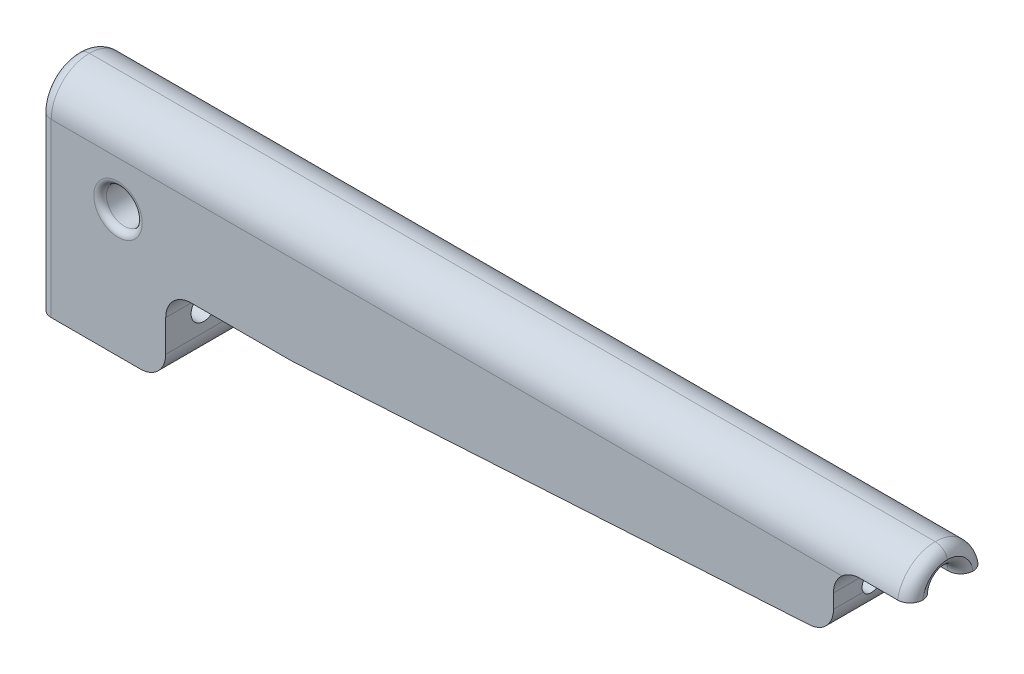
SolidWorks part; units mm, degrees
material "Acetal-Delrin 100 Black"
ref_plane "Front Plane" through (0, 0, 0) normal (0, 0, 1) x (1, 0, 0)
ref_plane "Top Plane" through (0, 0, 0) normal (0, 1, 0) x (1, 0, 0)
ref_plane "Right Plane" through (0, 0, 0) normal (1, 0, 0) x (0, 0, -1)
sketch "Sketch1" plane through (0, 0, 0) normal (0, 0, 1) x (1, 0, 0)
  line L0 (-0.1915, 12.7) -> (-50000.1915, 12.7) construction
  line L1 (25.4, 0) -> (173.99, 0)
  line L2 (0, 0) -> (0, 25.4)
  line L4 (173.99, 0) -> (173.99, 25.4)
  line L5 (173.99, 25.4) -> (0, 25.4)
  line L6 (0, 0) -> (0, -16.51)
  line L7 (0, -16.51) -> (25.4, -16.51)
  line L8 (25.4, -16.51) -> (25.4, 0)
  point P7 (0, 12.7)
  dimension "D1" = 25.4
  dimension "D3" = 16.51
  dimension "D2" = 173.99
  dimension "D4" = 25.4
  dimension "D6" = 25.4
extrude "Boss-Extrude1" add sketch "Sketch1" against normal blind 15.24
fillet "Fillet2" radius 7.62 2 edges at (86.995, 25.4, 0) (86.995, 25.4, -15.24)
sketch "Sketch2" plane through (0, 0, 0) normal (0, 0, 1) x (1, 0, 0)
  line L0 (158.75, 19.05) -> (158.75, 6.35)
  line L2 (25.4, 0) -> (173.99, 0) construction
  line L3 (50.8, 0) -> (153.899, 0)
  line L4 (158.75, 19.05) -> (173.99, 19.05)
  line L5 (0, 17.78) -> (0, -16.51) construction
  line L6 (173.99, 0) -> (173.99, 17.78) construction
  line L7 (173.99, 19.05) -> (173.99, 0)
  line L8 (173.99, 0) -> (153.899, 0)
  line L9 (158.75, 6.35) -> (50.8, 0)
  dimension "D1" = 19.05
  dimension "D2" = 50.8
  dimension "D3" = 15.24
  dimension "D4" = 12.7
extrude "Cut-Extrude1" cut sketch "Sketch2" against normal through all
sketch "Sketch3" plane through (0, 0, 0) normal (0, 0, 1) x (1, 0, 0)
  line L0 (0, 8.89) -> (158.75, 8.89) construction
  line L1 (0, 17.78) -> (0, -16.51) construction
  line L2 (0, 0) -> (0, 17.78) construction
  line L3 (0, 17.78) -> (0, -16.51) construction
  line L4 (158.75, 17.78) -> (158.75, 6.35) construction
  point P6 (15.875, 8.89)
  point P10 (0, 8.89)
  dimension "D1" = 15.875
hole_wizard "9/32 (0.28125) Diameter Hole1" positions "3DSketch1" profile "Sketch4" hole size "9/32" standard "ANSI Inch" end condition through all
sketch3d "3DSketch1"
  point P0 (15.875, 8.89, 0)
sketch "Sketch4" plane through (15.875, 8.89, 0) normal (1, 0, 0) x (0, -1, 0)
  line L0 (0, 0) -> (0, 15.24)
  line L1 (0, 15.24) -> (3.5719, 15.24)
  line L2 (3.5719, 15.24) -> (3.5719, 0)
  line L5 (3.5719, 0) -> (0, 0)
  line L11 (0, -6.35) -> (0, 107.95) construction
  dimension "Thru Hole Dia." = 7.1437
  dimension "Thru Hole Depth" = 15.24
sketch "Sketch5" plane through (158.75, 0, 0) normal (1, 0, 0) x (0, 0, -1)
  line L0 (0, 12.065) -> (15.24, 12.065) construction
  line L1 (0, 17.78) -> (0, 6.35) construction
  line L2 (15.24, 17.78) -> (15.24, 6.35) construction
  line L3 (7.62, 19.05) -> (7.62, 6.35) construction
  line L4 (15.1334, 19.05) -> (0.1066, 19.05) construction
  line L5 (15.24, 6.35) -> (0, 6.35) construction
  point P12 (7.62, 12.065)
hole_wizard "#10-24 Tapped Hole1" positions "3DSketch2" profile "Sketch6" tap size "#10-24" standard "ANSI Inch"
sketch3d "3DSketch2"
  point P0 (158.75, 12.065, -7.62)
sketch "Sketch6" plane through (158.75, 12.065, -7.62) normal (0, 1, 0) x (0, 0, -1)
  line L0 (0, 0) -> (0, 58.2908)
  line L1 (0, 58.2908) -> (1.8986, 57.15)
  line L2 (1.8986, 57.15) -> (1.8986, 0)
  line L5 (1.8986, 0) -> (0, 0)
  line L10 (0, 58.2908) -> (-1.8987, 57.15) construction
  line L11 (0, -6.35) -> (0, 107.95) construction
  dimension "Tap Drill Dia." = 3.7973
  dimension "Tap Drill Depth" = 57.15
  dimension "Drill Angle" = 118
cosmetic thread "Hole Thread1" parameters "D1"=50.8, "D2"=4.826
sketch "Sketch7" plane through (173.99, 0, 0) normal (1, 0, 0) x (0, 0, -1)
  line L0 (15.1334, 19.05) -> (0.1066, 19.05) construction
  circle A0 centre (7.62, 19.05) radius 2.5718
extrude "Cut-Extrude2" cut sketch "Sketch7" against normal blind 6.35 contours A0
fillet "Fillet7" radius 5.08 4 edges at (158.75, 6.35, -7.62) (158.75, 19.05, -7.62) (25.4, 0, -7.62) (25.4, -16.51, -7.62)
fillet "Fillet8" radius 2.54 3 edges at (173.99, 21.6218, -7.62) (173.99, 23.5999, -12.5387) (173.99, 23.5999, -2.7013)
fillet "Fillet9" radius 2.54 1 edges at (167.64, 21.6218, -7.62)
fillet "Fillet10" radius 2.54 4 edges at (0, 0.635, 0) (0, 0.635, -15.24) (0, 23.1682, -13.0082) (0, 23.1682, -2.2318)
fillet "Fillet11" radius 1.27 2 edges at (19.4469, 8.89, 0) (19.4469, 8.89, -15.24)
sketch "Sketch8" plane through (0, 0, 0) normal (-1, 0, 0) x (0, 0, 1)
  line L0 (-7.62, -16.51) -> (-7.62, 22.86) construction
  line L1 (-12.7, -16.51) -> (-2.54, -16.51) construction
  point P0 (-7.62, -6.985)
  dimension "D1" = 15.875
hole_wizard "1/4-20 Tapped Hole1" positions "Sketch10" profile "Sketch9" tap size "1/4-20" standard "ANSI Inch"
sketch "Sketch10" plane through (0, 0, 0) normal (-1, 0, 0) x (0, 0, 1)
  point P0 (-7.62, -6.985)
sketch "Sketch9" plane through (0, -6.985, -7.62) normal (0, 1, 0) x (0, 0, 1)
  line L0 (0, 0) -> (0, 28.9658)
  line L1 (0, 28.9658) -> (2.5527, 27.432)
  line L2 (2.5527, 27.432) -> (2.5527, 0)
  line L5 (2.5527, 0) -> (0, 0)
  line L10 (0, 28.9658) -> (-2.5527, 27.432) construction
  line L11 (0, -6.35) -> (0, 107.95) construction
  dimension "Tap Drill Dia." = 5.1054
  dimension "Tap Drill Depth" = 27.432
  dimension "Drill Angle" = 118
cosmetic thread "Hole Thread2" parameters "D1"=20.32, "D2"=6.35
